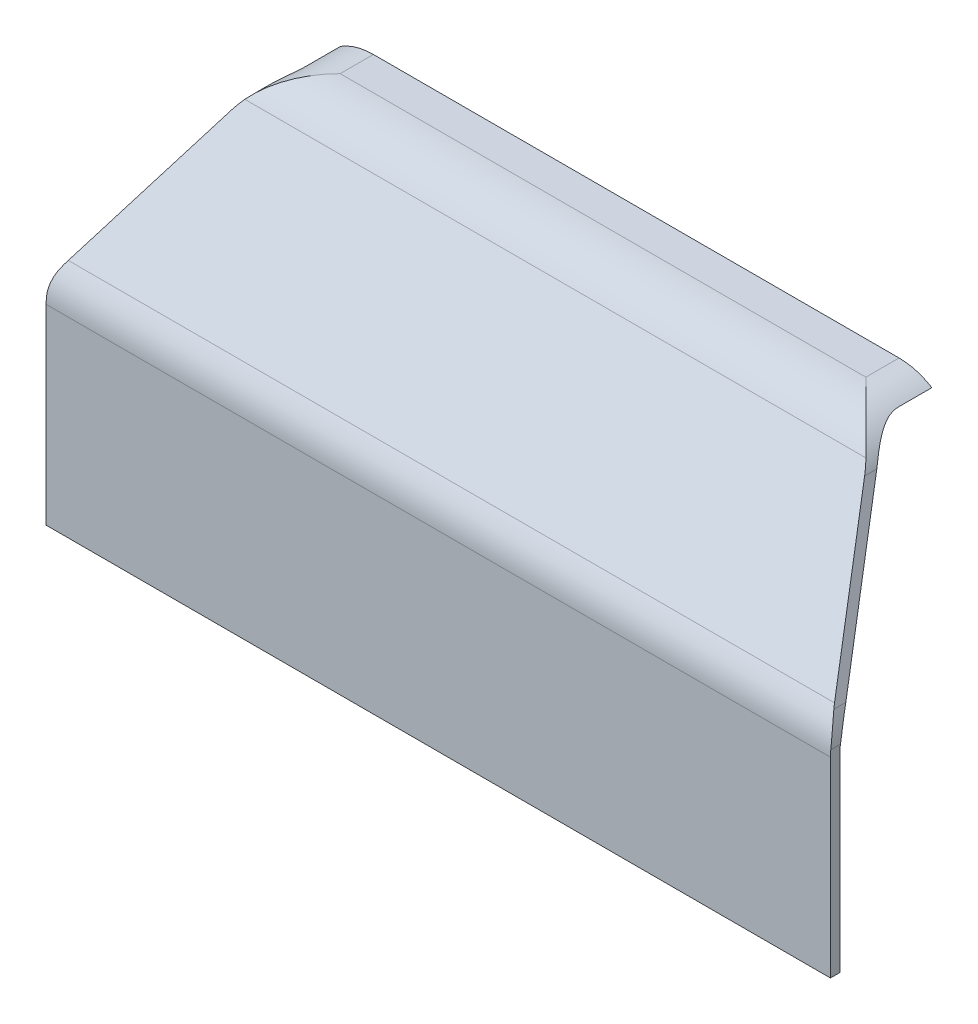
SolidWorks part; units mm, degrees
ref_plane "Alzado" through (0, 0, 0) normal (0, 0, 1) x (1, 0, 0)
ref_plane "Planta" through (0, 0, 0) normal (0, 1, 0) x (1, 0, 0)
ref_plane "Vista lateral" through (0, 0, 0) normal (1, 0, 0) x (0, 0, -1)
sketch "Croquis1" plane through (0, 0, 0) normal (1, 0, 0) x (0, 0, -1)
  line L0 (0, 0) -> (0, 66.9081)
  line L1 (0, 66.9081) -> (41.9998, 116.9615)
  line L2 (41.9998, 116.9615) -> (60.6009, 116.9615)
  line L3 (60.6009, 116.9615) -> (60.6009, 119.9615)
  line L4 (60.6009, 119.9615) -> (40.6009, 119.9615)
  line L5 (40.6009, 119.9615) -> (-3, 68)
  line L6 (-3, 68) -> (-3, 0)
  line L7 (-3, 0) -> (0, 0)
  line L8 (0, 66.9081) -> (29.2398, 66.9081) construction
  dimension "D1" = 3
  dimension "D2" = 3
  dimension "D3" = 3
  dimension "D4" = 68
  dimension "D5" = 119.9615
  dimension "D6" = 20
  dimension "D7" = 50
extrude "Saliente-Extruir1" add sketch "Croquis1" along normal mid plane 252
fillet "Redondeo1" radius 18 1 edges at (0, 68, 3)
fillet "Redondeo2" radius 20 1 edges at (0, 119.9615, -40.6009)
fillet "Redondeo3" radius 17 1 edges at (0, 116.9615, -41.9998)
fillet "Redondeo4" radius 17 1 edges at (0, 66.9081, 0)
sketch "Croquis2" plane through (0, 0, 3) normal (0, 0, 1) x (1, 0, 0)
  line L29 (-96, 119.9615) -> (-126, 68)
  line L35 (-96, 119.9615) -> (-126, 119.9615)
  line L36 (-126, 119.9615) -> (-126, 68)
  dimension "D5" = 60
extrude "Cortar-Extruir1" cut sketch "Croquis2" against normal through all
mirror "Simetría1" about plane through (0, 0, 0) normal (1, 0, 0) of "Cortar-Extruir1"
fillet "Redondeo5" radius 17 2 edges at (-126, 68, 0.064) (126, 68, 0.064)
sketch "Croquis5" plane through (0, 0, -60.6009) normal (0, 0, -1) x (-1, 0, 0)
  line L0 (84.453, 119.9615) -> (96, 119.9615)
  line L1 (96, 119.9615) -> (101.7735, 109.9615)
  arc A0 (101.7735, 109.9615) -> (84.453, 119.9615) centre (84.453, 99.9615) ccw
extrude "Cortar-Extruir2" cut sketch "Croquis5" against normal through all
mirror "Simetría2" about plane through (0, 0, 0) normal (1, 0, 0) of "Cortar-Extruir2"
